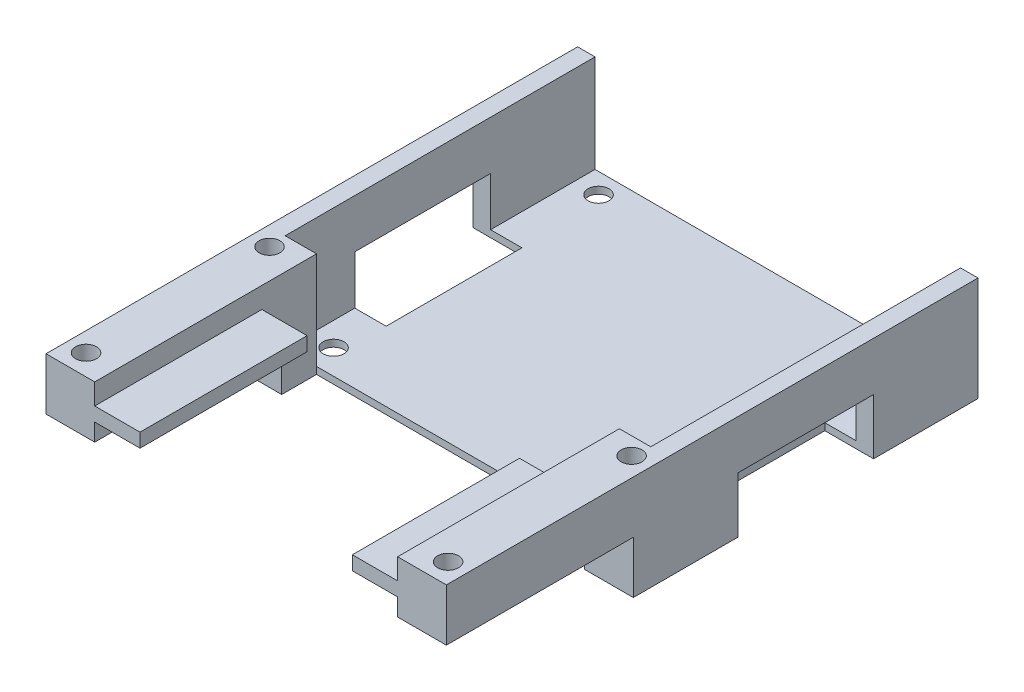
SolidWorks part; units mm, degrees
ref_plane "Front Plane" through (0, 0, 0) normal (0, 0, 1) x (1, 0, 0)
ref_plane "Top Plane" through (0, 0, 0) normal (0, 1, 0) x (1, 0, 0)
ref_plane "Right Plane" through (0, 0, 0) normal (1, 0, 0) x (0, 0, -1)
sketch "Sketch1" plane through (0, 0, 0) normal (0, 1, 0) x (1, 0, 0)
  line L0 (0, 0) -> (0, 76.35) construction
  line L1 (-28.75, 76.35) -> (28.75, 76.35)
  line L2 (28.75, 76.35) -> (28.75, 0)
  line L3 (28.75, 0) -> (21.75, 0)
  line L4 (21.75, 0) -> (21.75, 31.85)
  line L5 (21.75, 31.85) -> (-21.75, 31.85)
  line L6 (-21.75, 31.85) -> (-21.75, 0)
  line L7 (-21.75, 0) -> (-28.75, 0)
  line L8 (-28.75, 0) -> (-28.75, 76.35)
  line L9 (-26.25, 76.35) -> (-26.25, 31.85)
  line L14 (-26.25, 31.85) -> (-21.75, 31.85)
  line L15 (26.25, 76.35) -> (26.25, 31.85)
  line L16 (26.25, 31.85) -> (21.75, 31.85)
  line L17 (28.75, 74.35) -> (30.25, 74.35)
  line L18 (-28.75, 41.35) -> (-26.25, 41.35)
  line L19 (-28.75, 41.35) -> (-28.75, 53.35)
  line L20 (-28.75, 53.35) -> (-26.25, 53.35)
  line L21 (-26.25, 41.35) -> (-26.25, 53.35)
  line L22 (30.25, 68.35) -> (28.75, 68.35)
  line L23 (-30.25, 68.35) -> (-28.75, 68.35)
  line L24 (-28.75, 74.35) -> (-30.25, 74.35)
  arc A0 (30.25, 68.35) -> (30.25, 74.35) centre (30.25, 71.35) ccw
  arc A1 (-30.25, 68.35) -> (-30.25, 74.35) centre (-30.25, 71.35) cw
  point P10 (0, 76.35)
  point P16 (-27.5, 41.35)
  point P17 (-22.85, 73.45)
  point P18 (22.85, 73.45)
  point P23 (22.85, 35.4)
  point P24 (-22.85, 35.4)
  point P25 (26, 3)
  point P26 (26, 29.35)
  point P27 (-26, 29.35)
  point P28 (-26, 3)
  point P40 (30.25, 71.35)
  point P41 (-30.25, 71.35)
  dimension "D16" = 3
  dimension "D1" = 2.5
  dimension "D2" = 7
  dimension "D3" = 43.5
  dimension "D4" = 31.85
  dimension "D5" = 44.5
  dimension "D6" = 23
  dimension "D7" = 12
  dimension "D8" = 22.85
  dimension "D9" = 38.05
  dimension "D10" = 2.9
  dimension "D11" = 52
  dimension "D12" = 52
  dimension "D13" = 47
  dimension "D14" = 3
  dimension "D15" = 1.5
  dimension "D17" = 2
extrude "Boss-Extrude1" add sketch "Sketch1" along normal blind 1 contours L5 L0 L1 L9 L14 | L0 L5 L16 L15 L1 region at (-13.125, 0, -54.1) region at (13.125, 0, -54.1)
extrude "Boss-Extrude2" add sketch "Sketch1<3>" along normal blind 15 contours L18 L8 L7 L6 L14 L9 | L8 L20 L9 L1 | L15 L16 L4 L3 L2 L1 | L20 L8 L18 L9 region at (-27.5, 0, -64.85) region at (25.999, 0, -28.6329) region at (-27.5, 0, -47.35) region at (-25.4666, 0, -17.9154)
sketch "Sketch1<3>" plane through (0, 0, 0) normal (0, 1, 0) x (1, 0, 0) same geometry as "Sketch1"
hole_wizard "Ø3.0 (3) Diameter Hole1" positions "Sketch4" profile "Sketch5" hole size "Ø3.0" standard "ANSI Metric" end condition through all
sketch "Sketch4" plane through (0, 0, 0) normal (0, -1, 0) x (-1, 0, 0)
  point P0 (-22.85, 73.45)
  point P3 (22.85, 73.45)
  point P6 (26, 29.35)
  point P9 (22.85, 35.4)
  point P12 (-22.85, 35.4)
  point P15 (-26, 29.35)
  point P18 (-26, 3)
  point P21 (26, 3)
  point P24 (-30.25, 71.35)
  point P27 (30.25, 71.35)
sketch "Sketch5" plane through (22.85, 0, -73.45) normal (1, 0, 0) x (0, 0, -1)
  line L0 (0, 0) -> (0, 15)
  line L1 (0, 15) -> (1.5, 15)
  line L2 (1.5, 15) -> (1.5, 0)
  line L5 (1.5, 0) -> (0, 0)
  line L11 (0, -6.35) -> (0, 107.95) construction
  dimension "Thru Hole Dia." = 3
  dimension "Thru Hole Depth" = 15
sketch "Sketch6" plane through (0, 0, 0) normal (0, 0, 1) x (1, 0, 0)
  line L0 (-21.75, 15) -> (-21.75, 0) construction
  line L5 (0, -1.6497) -> (0, 21.9352) construction
  line L6 (-21.75, 10) -> (-15.25, 10)
  line L7 (-21.75, 10) -> (-21.75, 12)
  line L8 (-21.75, 12) -> (-15.25, 12)
  line L9 (-15.25, 10) -> (-15.25, 12)
  line L10 (-28.75, 15) -> (-28.75, 0) construction
  line L11 (-20.25, 10) -> (-21.75, 10)
  line L12 (-20.25, 10) -> (-20.25, 7.5)
  line L13 (-20.25, 7.5) -> (-21.75, 7.5)
  line L14 (-21.75, 10) -> (-21.75, 7.5)
  line L15 (-21.75, 0) -> (-28.75, 0)
  line L16 (-21.75, 0) -> (-21.75, 7.5)
  line L17 (-21.75, 7.5) -> (-28.75, 7.5)
  line L18 (-28.75, 0) -> (-28.75, 7.5)
  line L19 (28.75, 0) -> (28.75, 7.5)
  line L20 (21.75, 7.5) -> (28.75, 7.5)
  line L21 (21.75, 0) -> (21.75, 7.5)
  line L22 (21.75, 0) -> (28.75, 0)
  line L23 (21.75, 10) -> (21.75, 7.5)
  line L24 (20.25, 7.5) -> (21.75, 7.5)
  line L25 (20.25, 10) -> (20.25, 7.5)
  line L26 (20.25, 10) -> (21.75, 10)
  line L27 (15.25, 10) -> (15.25, 12)
  line L28 (21.75, 12) -> (15.25, 12)
  line L29 (21.75, 10) -> (21.75, 12)
  line L30 (21.75, 10) -> (15.25, 10)
  line L31 (-21.75, 15) -> (-28.75, 15) construction
  line M21 (21.75, 0) -> (28.75, 0)
  line M22 (28.75, 0) -> (28.75, 15)
  line M24 (21.75, 15) -> (21.75, 0)
  dimension "D1" = 6.5
  dimension "D2" = 3
  dimension "D3" = 2
  dimension "D4" = 2.5
  dimension "D5" = 1.5
extrude "Boss-Extrude3" add sketch "Sketch6" against normal blind 24 contours L30 L26 L28 L27 M24 | L6 L9 L8 L7 region at (-18.5, 11, 0) region at (18.5, 11, 0)
extrude "Cut-Extrude1" cut sketch "Sketch6<4>" against normal blind 26.85 contours L18 L15 L16 L17 | L20 M24 M21 M22 region at (-25.25, 3.75, 0) region at (25.25, 3.75, 0)
sketch "Sketch6<4>" plane through (0, 0, 0) normal (0, 0, 1) x (1, 0, 0) same geometry as "Sketch6"
sketch "Sketch8" plane through (0, 0, 0) normal (0, -1, 0) x (1, 0, 0)
  line L0 (0, 17.5937) -> (0, -89.2896) construction
  line L1 (-28.75, -61.35) -> (-21.75, -61.35)
  line L2 (-28.75, -61.35) -> (-28.75, -41.85)
  line L3 (-28.75, -41.85) -> (-21.75, -41.85)
  line L4 (-21.75, -61.35) -> (-21.75, -41.85)
  line L6 (-28.75, -76.35) -> (28.75, -76.35) construction
  line L8 (21.75, -61.35) -> (21.75, -41.85)
  line L9 (28.75, -41.85) -> (21.75, -41.85)
  line L10 (28.75, -61.35) -> (28.75, -41.85)
  line L11 (28.75, -61.35) -> (21.75, -61.35)
  line L12 (-28.75, -26.85) -> (-28.75, -76.35) construction
  dimension "D1" = 15
  dimension "D2" = 7
  dimension "D3" = 19.5
extrude "Cut-Extrude2" cut sketch "Sketch8" against normal blind 8
sketch "Sketch9" plane through (0, 0, 0) normal (0, -1, 0) x (1, 0, 0)
  line L0 (-3.6898, -66.9636) -> (-0.7669, -56.1918)
  line L1 (-0.7669, -56.1918) -> (-9.5993, -56.1918)
  line L2 (-9.5993, -56.1918) -> (4.2079, -40.0618)
  line L3 (4.2079, -40.0618) -> (3.001, -51.0446)
  line L4 (3.001, -51.0446) -> (10.9951, -51.0446)
  line L5 (10.9951, -51.0446) -> (-3.6898, -66.9636)
extrude "Cut-Extrude3" cut sketch "Sketch9" against normal blind 0.3
equation "\"D1@Boss-Extrude2\"=16.000000mm-1"
